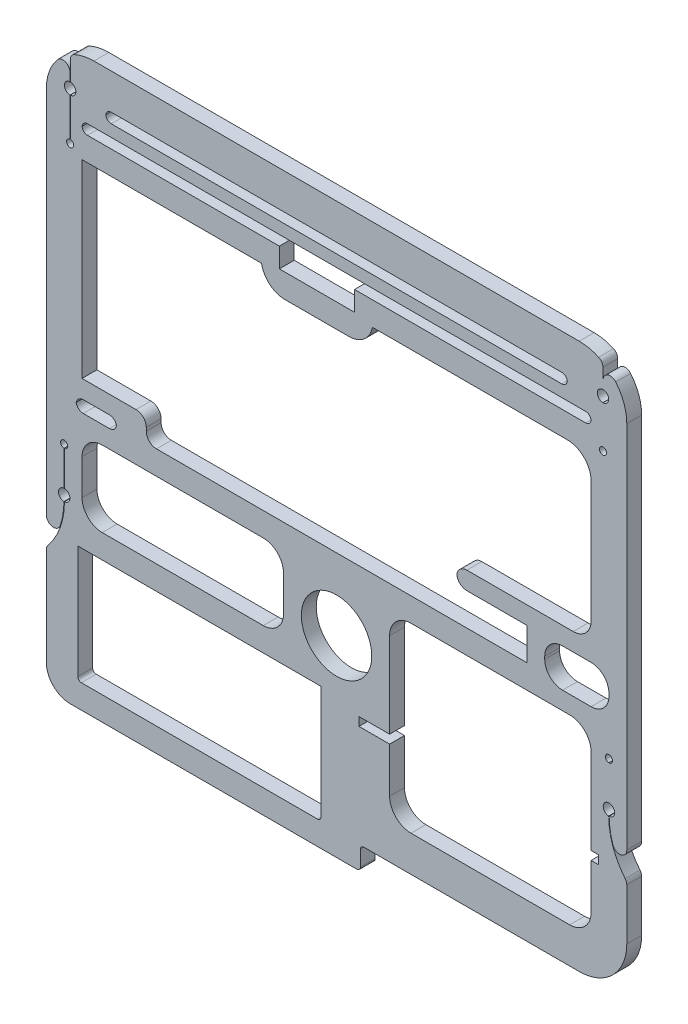
SolidWorks part; units mm, degrees
ref_plane "Front Plane" through (0, 0, 0) normal (0, 0, 1) x (1, 0, 0)
ref_plane "Top Plane" through (0, 0, 0) normal (0, 1, 0) x (1, 0, 0)
ref_plane "Right Plane" through (0, 0, 0) normal (1, 0, 0) x (0, 0, -1)
sketch "Sketch1" plane through (0, 0, 0) normal (0, 0, 1) x (1, 0, 0)
  line L0 (63.9883, 88.3985) -> (63.9883, 84.5885) construction
  line L1 (48.2422, 30.1083) -> (110.2188, 30.1083)
  line L2 (48.2422, 30.1083) -> (48.2422, 88.3985)
  line L3 (48.2422, 88.3985) -> (110.2188, 88.3985)
  line L4 (110.2188, 30.1083) -> (110.2188, 88.3985)
  line L5 (106.4088, 84.5885) -> (52.0522, 84.5885)
  line L6 (106.4088, 84.5885) -> (106.4088, 33.9183)
  line L7 (106.4088, 33.9183) -> (52.0522, 33.9183)
  line L8 (52.0522, 84.5885) -> (52.0522, 33.9183)
  line L9 (63.9883, 86.4935) -> (18.0707, 86.4935) construction
  line L10 (52.0522, 41.2855) -> (48.2422, 41.2855) construction
  line L11 (50.1472, 41.2855) -> (50.1472, 25.8577) construction
  line L12 (13.5248, 33.9183) -> (13.5248, 30.1083) construction
  line L13 (13.5248, 32.0133) -> (21.1598, 32.0133) construction
  line L14 (110.2188, 38.1916) -> (106.4088, 38.1916) construction
  line L15 (108.3138, 38.1916) -> (108.3138, 22.3321) construction
  line L16 (106.4088, 54.6152) -> (106.4088, 79.5085) construction
  line L17 (52.0522, 74.5555) -> (52.0522, 54.6152) construction
  line L22 (79.0876, 86.4935) -> (79.6338, 86.4935) construction
  line L23 (96.5564, 32.0133) -> (96.0102, 32.0133) construction
  dimension "D1" = 3.81
  dimension "D2" = 3.81
extrude "Boss-Extrude1" add sketch "Sketch1" along normal blind 1.5875
sketch "Sketch2" plane through (0, 0, 0) normal (0, 0, -1) x (-1, 0, 0)
  line L0 (-106.4088, 33.9183) -> (-106.4088, 84.5885) construction
  line L1 (-106.4088, 55.8724) -> (-52.0522, 55.8724)
  line L2 (-106.4088, 55.8724) -> (-106.4088, 53.3324)
  line L3 (-106.4088, 53.3324) -> (-52.0522, 53.3324)
  line L4 (-52.0522, 55.8724) -> (-52.0522, 53.3324)
  line L5 (-52.0522, 84.5885) -> (-52.0522, 33.9183) construction
  line L7 (-99.5505, 55.8724) -> (-58.9105, 55.8724) construction
  line L8 (-99.4108, 81.1849) -> (-61.0568, 81.1849) construction
  line L9 (-80.5132, 79.0767) -> (-73.7568, 79.0767) construction
  line L10 (-80.5132, 81.1849) -> (-80.5132, 79.0767) construction
  line L11 (-106.4088, 81.1849) -> (-81.1482, 81.1849)
  line L12 (-106.4088, 81.1849) -> (-106.4088, 78.6449)
  line L13 (-106.4088, 78.6449) -> (-83.0532, 78.6449)
  line L14 (-52.0522, 81.1849) -> (-52.0522, 78.6449)
  line L15 (-106.4088, 83.5217) -> (-52.0522, 83.5217)
  line L16 (-106.4088, 83.5217) -> (-106.4088, 82.2517)
  line L17 (-106.4088, 82.2517) -> (-52.0522, 82.2517)
  line L18 (-52.0522, 83.5217) -> (-52.0522, 82.2517)
  line L19 (-73.7568, 79.0767) -> (-73.7568, 81.1849) construction
  line L20 (-80.5132, 81.1849) -> (-80.5132, 79.0767) construction
  line L21 (-73.7568, 79.0767) -> (-73.7568, 81.1849) construction
  line L22 (-81.1482, 79.0767) -> (-81.1482, 81.1849)
  line L23 (-73.1218, 79.0767) -> (-81.1482, 79.0767)
  line L24 (-73.1218, 79.0767) -> (-73.1218, 81.1849)
  line L25 (-83.0532, 78.6449) -> (-83.0532, 76.5367)
  line L26 (-83.0532, 76.5367) -> (-71.2168, 76.5367)
  line L27 (-71.2168, 76.5367) -> (-71.2168, 78.6449)
  line L28 (-71.2168, 78.6449) -> (-52.0522, 78.6449)
  line L29 (-73.1218, 81.1849) -> (-52.0522, 81.1849)
  line L30 (-81.1482, 71.7401) -> (-80.5132, 71.7401) construction
  line L31 (-57.9086, 84.5885) -> (-57.9086, 83.5217) construction
  line L32 (-73.7568, 71.6584) -> (-73.1218, 71.6584) construction
  line L33 (-106.4088, 84.5885) -> (-52.0522, 84.5885) construction
  line L35 (-57.9086, 82.2517) -> (-57.9086, 81.1849) construction
  dimension "D1" = 2.54
  dimension "D2" = 1.905
  dimension "D3" = 2.54
  dimension "D4" = 1.905
  dimension "D5" = 1.27
  dimension "D6" = 0.635
extrude "Boss-Extrude2" add sketch "Sketch2" against normal up to surface (1.5875 mm away) up to face at (79.2305, 59.2534, 1.5875)
sketch "Sketch14" plane through (0, 0, 1.5875) normal (0, 0, 1) x (1, 0, 0)
  line L0 (77.0492, 42.694) -> (51.5984, 42.694) construction
  line L1 (84.8947, 41.932) -> (84.8947, 50.7924) construction
  line L2 (84.8947, 33.9183) -> (84.8947, 53.3324)
  line L4 (77.0492, 42.694) -> (52.0522, 42.694)
  line L5 (52.0522, 53.3324) -> (52.0522, 33.9183) construction
  line L6 (52.0522, 53.3324) -> (106.4088, 53.3324) construction
  line L7 (52.0522, 33.9183) -> (106.4088, 33.9183) construction
  line L9 (77.0492, 42.694) -> (77.0492, 33.9183)
  line L10 (77.0492, 33.9183) -> (84.8947, 33.9183)
  line L11 (52.0522, 53.3324) -> (84.8947, 53.3324)
  line L12 (52.0522, 53.3324) -> (52.0522, 42.694)
extrude "Boss-Extrude9" add sketch "Sketch14" against normal up to surface (1.5875 mm away) up to face at (78.1827, 80.9246, 0)
sketch "Sketch5" plane through (0, 0, 0) normal (0, 0, -1) x (-1, 0, 0)
  line L1 (-51.5984, 30.2353) -> (-77.5572, 30.2353) construction
  line L2 (-51.5984, 30.2353) -> (-51.5984, 42.694) construction
  line L6 (-51.5984, 42.694) -> (-77.5572, 42.694) construction
  line L7 (-77.5572, 30.2353) -> (-77.5572, 42.694) construction
  line L8 (-51.5984, 30.2353) -> (-77.5572, 30.2353)
  line L9 (-51.5984, 30.2353) -> (-51.5984, 42.694)
  line L10 (-51.5984, 42.694) -> (-77.5572, 42.694)
  line L11 (-77.5572, 30.2353) -> (-77.5572, 42.694)
  circle A1 centre (-79.2305, 48.2171) radius 3.7592 construction
  circle A2 centre (-79.2305, 48.2171) radius 3.7592
extrude "Cut-Extrude1" cut sketch "Sketch5" against normal up to surface (1.5875 mm away) up to face at (64.5507, 38.3062, 1.5875)
fillet "Fillet1" radius 5.08 3 edges at (110.2188, 30.1083, 0.7937) (48.2422, 88.3985, 0.7937) (110.2188, 88.3985, 0.7937)
fillet "Fillet2" radius 2.54 3 edges at (71.2168, 76.5367, 0.7937) (106.4088, 78.6449, 0.7937) (83.0532, 76.5367, 0.7937)
fillet "Fillet4" radius 0.5842 4 edges at (52.0522, 81.1849, 0.7937) (52.0522, 82.2517, 0.7938) (106.4088, 82.2517, 0.7937) (106.4088, 81.1849, 0.7937)
sketch "Sketch6" plane through (0, 0, 0) normal (0, 0, -1) x (-1, 0, 0)
  circle A0 centre (-107.6788, 84.5885) radius 0.6096 construction
  circle A1 centre (-50.7822, 84.5885) radius 0.6096 construction
  circle A2 centre (-108.3138, 46.6777) radius 0.6096 construction
  circle A3 centre (-50.1472, 46.6777) radius 0.6096 construction
  circle A4 centre (-107.6788, 84.5885) radius 0.6096
  circle A5 centre (-50.7822, 84.5885) radius 0.6096
  circle A6 centre (-108.3138, 46.6777) radius 0.6096
  circle A7 centre (-50.1472, 46.6777) radius 0.6096
extrude "Cut-Extrude2" cut sketch "Sketch6" against normal up to surface (1.5875 mm away) up to face at (75.4713, 48.2171, 1.5875)
sketch "Sketch9" plane through (0, 0, 1.5875) normal (0, 0, 1) x (1, 0, 0)
  line L4 (107.199, 41.932) -> (81.6212, 41.932)
  line L5 (81.6212, 41.932) -> (81.6212, 41.0176)
  line L6 (81.6212, 41.0176) -> (107.199, 41.0176)
  line L7 (107.199, 41.0176) -> (107.199, 41.932)
  line L8 (107.199, 41.932) -> (81.6212, 41.932)
  line L9 (81.6212, 41.932) -> (81.6212, 41.0176)
  line L10 (81.6212, 41.0176) -> (107.199, 41.0176)
  line L11 (107.199, 41.0176) -> (107.199, 41.932)
  dimension "D1" = 0
extrude "Cut-Extrude3" cut sketch "Sketch9" against normal up to surface (1.5875 mm away) up to face at (49.5376, 46.6777, 0)
sketch "Sketch11" plane through (0, 0, 1.5875) normal (0, 0, 1) x (1, 0, 0)
  line L0 (51.5984, 30.2353) -> (77.5572, 30.2353) construction
  line L1 (48.2422, 30.1083) -> (81.7705, 30.1083)
  line L2 (48.2422, 30.1083) -> (48.2422, 27.6953)
  line L3 (48.2422, 27.6953) -> (81.7705, 27.6953)
  line L4 (81.7705, 30.1083) -> (81.7705, 27.6953)
  line L5 (79.2305, 51.9763) -> (79.2305, -22.2214) construction
  circle A0 centre (79.2305, 48.2171) radius 3.7592 construction
  dimension "D1" = 2.54
  dimension "D2" = 2.54
extrude "Boss-Extrude6" add sketch "Sketch11" against normal up to surface (1.5875 mm away) up to face at (95.2379, 42.1917, 0)
fillet "Fillet7" radius 2.54 1 edges at (48.2422, 27.6953, 0.7937)
fillet "Fillet8" radius 0.381 2 edges at (81.7705, 27.6953, 0.7937) (81.7705, 30.1083, 0.7937)
sketch "Sketch12" plane through (0, 0, 1.5875) normal (0, 0, 1) x (1, 0, 0)
  line L0 (52.0522, 84.5885) -> (52.0522, 83.5217) construction
  line L1 (52.0522, 84.5885) -> (54.5922, 84.5885)
  line L2 (52.0522, 84.5885) -> (52.0522, 83.5217)
  line L3 (52.0522, 83.5217) -> (54.5922, 83.5217)
  line L4 (54.5922, 84.5885) -> (54.5922, 83.5217)
  line L5 (106.4088, 84.5885) -> (52.0522, 84.5885) construction
  line L6 (106.4088, 83.5217) -> (52.0522, 83.5217) construction
  line L8 (106.4088, 84.5885) -> (103.8688, 84.5885)
  line L9 (106.4088, 84.5885) -> (106.4088, 83.5217)
  line L10 (106.4088, 83.5217) -> (103.8688, 83.5217)
  line L11 (103.8688, 84.5885) -> (103.8688, 83.5217)
  dimension "D1" = 2.54
extrude "Boss-Extrude7" add sketch "Sketch12" against normal up to surface (1.5875 mm away) up to face at (95.2379, 42.1917, 0)
fillet "Fillet11" radius 0.5842 4 edges at (103.8688, 83.5217, 0.7937) (103.8688, 84.5885, 0.7937) (54.5922, 83.5217, 0.7937) (54.5922, 84.5885, 0.7937)
sketch "Sketch13" plane through (0, 0, 1.5875) normal (0, 0, 1) x (1, 0, 0)
  line L0 (50.7695, 86.0858) -> (50.7695, 85.198) construction
  line L1 (50.7949, 85.198) -> (50.7949, 87.2592) construction
  line L2 (50.7695, 83.9791) -> (50.7695, 79.8893) construction
  line L3 (50.7949, 79.8893) -> (50.7949, 83.9791) construction
  line L4 (107.6661, 85.198) -> (107.6661, 87.2592) construction
  line L5 (107.6915, 83.9791) -> (107.6915, 79.8893) construction
  line L6 (107.6661, 79.8893) -> (107.6661, 83.9791) construction
  line L7 (108.3265, 50.9963) -> (108.3265, 47.2872) construction
  line L8 (108.3011, 50.9963) -> (108.3011, 47.2872) construction
  line L9 (50.1345, 50.9963) -> (50.1345, 47.2872) construction
  line L10 (50.1599, 50.9963) -> (50.1599, 47.2872) construction
  line L11 (50.7695, 86.0858) -> (50.7695, 85.198)
  line L12 (50.7949, 85.198) -> (50.7949, 87.2592)
  line L13 (50.7695, 83.9791) -> (50.7695, 79.8893)
  line L14 (50.7949, 79.8893) -> (50.7949, 83.9791)
  line L15 (107.6661, 85.198) -> (107.6661, 87.2592)
  line L16 (107.6915, 83.9791) -> (107.6915, 79.8893)
  line L17 (107.6661, 79.8893) -> (107.6661, 83.9791)
  line L18 (108.3265, 50.9963) -> (108.3265, 47.2872)
  line L19 (108.3011, 50.9963) -> (108.3011, 47.2872)
  line L20 (50.1345, 50.9963) -> (50.1345, 47.2872)
  line L21 (50.1599, 50.9963) -> (50.1599, 47.2872)
  line L22 (48.2422, 83.3185) -> (48.2422, 30.2353) construction
  line L23 (110.2188, 35.1883) -> (110.2188, 83.3185) construction
  line L24 (48.2422, 43.8754) -> (48.2422, 40.6699)
  line L25 (110.2188, 40.6699) -> (110.2188, 43.8754)
  line L26 (107.6915, 83.9791) -> (107.6915, 79.8893)
  line L27 (107.6915, 86.0858) -> (107.6915, 85.198) construction
  line L28 (107.6915, 86.0858) -> (107.6915, 85.198)
  arc A0 (107.6661, 83.9791) -> (107.6915, 83.9791) centre (107.6788, 84.5885) ccw
  arc A1 (50.7695, 86.0858) -> (49.4225, 86.5742) centre (50.0075, 86.0858) ccw construction
  arc A2 (51.2454, 87.9546) -> (50.7949, 87.2592) centre (51.5569, 87.2592) ccw construction
  arc A3 (50.7695, 79.8893) -> (50.7949, 79.8893) centre (50.7822, 79.5085) ccw construction
  arc A4 (107.6661, 87.2592) -> (107.2156, 87.9546) centre (106.9041, 87.2592) ccw construction
  arc A5 (109.0384, 86.5742) -> (107.6915, 86.0858) centre (108.4535, 86.0858) ccw construction
  arc A6 (107.6661, 79.8893) -> (107.6915, 79.8893) centre (107.6788, 79.5085) ccw construction
  arc A7 (108.3265, 50.9963) -> (108.3011, 50.9963) centre (108.3138, 51.3771) ccw construction
  arc A8 (108.3392, 46.0687) -> (108.7338, 43.6346) centre (116.0396, 46.0681) ccw construction
  arc A9 (108.7338, 43.6346) -> (110.2188, 43.8754) centre (109.4568, 43.8754) ccw construction
  arc A10 (108.2884, 46.0687) -> (110.046, 41.153) centre (116.0396, 46.0681) ccw construction
  arc A11 (110.2188, 40.6699) -> (110.046, 41.153) centre (109.4568, 40.6699) ccw construction
  arc A12 (48.2422, 43.8754) -> (49.7271, 43.6346) centre (49.0042, 43.8754) ccw construction
  arc A13 (50.1599, 50.9963) -> (50.1345, 50.9963) centre (50.1472, 51.3771) ccw construction
  arc A14 (48.415, 41.153) -> (50.1726, 46.0687) centre (42.4214, 46.0681) ccw construction
  arc A15 (49.7271, 43.6346) -> (50.1218, 46.0687) centre (42.4214, 46.0681) ccw construction
  arc A16 (48.415, 41.153) -> (48.2422, 40.6699) centre (49.0042, 40.6699) ccw construction
  arc A17 (50.7695, 83.9791) -> (50.7949, 83.9791) centre (50.7822, 84.5885) ccw
  arc A18 (50.7695, 86.0858) -> (49.4225, 86.5742) centre (50.0075, 86.0858) ccw
  arc A19 (51.2454, 87.9546) -> (50.7949, 87.2592) centre (51.5569, 87.2592) ccw
  arc A20 (50.7695, 79.8893) -> (50.7949, 79.8893) centre (50.7822, 79.5085) ccw
  arc A21 (107.6661, 87.2592) -> (107.2156, 87.9546) centre (106.9041, 87.2592) ccw
  arc A22 (109.0384, 86.5742) -> (107.6915, 86.0858) centre (108.4535, 86.0858) ccw
  arc A23 (107.6661, 79.8893) -> (107.6915, 79.8893) centre (107.6788, 79.5085) ccw
  arc A24 (108.3265, 50.9963) -> (108.3011, 50.9963) centre (108.3138, 51.3771) ccw
  arc A25 (108.3392, 46.0687) -> (108.7338, 43.6346) centre (116.0396, 46.0681) ccw
  arc A26 (108.7338, 43.6346) -> (110.2188, 43.8754) centre (109.4568, 43.8754) ccw
  arc A27 (108.2884, 46.0687) -> (110.046, 41.153) centre (116.0396, 46.0681) ccw
  arc A28 (110.2188, 40.6699) -> (110.046, 41.153) centre (109.4568, 40.6699) ccw
  arc A29 (48.2422, 43.8754) -> (49.7271, 43.6346) centre (49.0042, 43.8754) ccw
  arc A30 (50.1599, 50.9963) -> (50.1345, 50.9963) centre (50.1472, 51.3771) ccw
  arc A31 (48.415, 41.153) -> (50.1726, 46.0687) centre (42.4214, 46.0681) ccw
  arc A32 (49.7271, 43.6346) -> (50.1218, 46.0687) centre (42.4214, 46.0681) ccw
  arc A33 (48.415, 41.153) -> (48.2422, 40.6699) centre (49.0042, 40.6699) ccw
  circle A34 centre (50.7822, 84.5885) radius 0.6096 construction
  circle A35 centre (107.6788, 84.5885) radius 0.6096 construction
  circle A36 centre (108.3138, 46.6777) radius 0.6096 construction
  circle A37 centre (50.1472, 46.6777) radius 0.6096 construction
  arc A38 (53.3222, 88.3985) -> (48.2422, 83.3185) centre (53.3222, 83.3185) ccw construction
  arc A39 (110.2188, 83.3185) -> (105.1388, 88.3985) centre (105.1388, 83.3185) ccw construction
  arc A40 (50.7949, 85.198) -> (50.7695, 85.198) centre (50.7822, 84.5885) ccw
  arc A41 (107.6661, 83.9791) -> (107.6915, 83.9791) centre (107.6788, 84.5885) ccw
  arc A42 (108.3265, 47.2872) -> (108.3011, 47.2872) centre (108.3138, 46.6777) ccw
  arc A43 (50.1218, 46.0687) -> (50.1726, 46.0687) centre (50.1472, 46.6777) ccw
  arc A44 (51.2454, 87.9546) -> (49.4225, 86.5742) centre (53.3222, 83.3185) ccw
  arc A45 (109.0384, 86.5742) -> (107.2156, 87.9546) centre (105.1388, 83.3185) ccw
  arc A46 (50.1599, 47.2872) -> (50.1345, 47.2872) centre (50.1472, 46.6777) ccw
  arc A47 (108.2884, 46.0687) -> (108.3392, 46.0687) centre (108.3138, 46.6777) ccw
  arc A48 (107.6915, 85.198) -> (107.6661, 85.198) centre (107.6788, 84.5885) ccw
extrude "Cut-Extrude4" cut sketch "Sketch13" against normal through all contours A48 L28 A22 A45 A21 L15 | L17 A23 L16 A0 | A47 A27 A28 L25 A26 A25 | A42 L18 A24 L19 | A43 A32 A29 L24 A33 A31 | A46 L21 A30 L20 | A19 A44 A18 L11 A40 L12 | L13 A20 L14 A17 region at (50.4642, 87.0334, 1.5875) region at (50.7822, 79.9586, 1.5875) region at (107.9968, 87.0334, 1.5875) region at (107.6788, 79.9586, 1.5875) region at (108.3138, 50.9944, 1.5875) region at (50.1472, 50.9944, 1.5875) region at (48.8136, 42.5993, 1.5875) region at (109.6474, 42.5993, 1.5875)
fillet "Fillet12" radius 2.286 4 edges at (106.4088, 33.9183, 0.7937) (106.4088, 53.3324, 0.7937) (84.8947, 33.9183, 0.7937) (84.8947, 53.3324, 0.7937)
fillet "Fillet13" radius 0.381 2 edges at (51.5984, 30.2353, 0.7937) (77.5572, 30.2353, 0.7937)
sketch "Sketch15" plane through (0, 0, 1.5875) normal (0, 0, 1) x (1, 0, 0)
  line L0 (73.5663, 51.1734) -> (73.5663, 47.393) construction
  line L1 (71.4073, 45.234) -> (54.2112, 45.234) construction
  line L2 (52.0522, 51.1734) -> (52.0522, 47.393) construction
  line L3 (54.2112, 53.3324) -> (71.4073, 53.3324) construction
  line L4 (73.5663, 51.1734) -> (73.5663, 47.393)
  line L5 (71.4073, 45.234) -> (54.2112, 45.234)
  line L6 (52.0522, 51.1734) -> (52.0522, 47.393)
  line L7 (54.2112, 53.3324) -> (71.4073, 53.3324)
  arc A0 (73.5663, 51.1734) -> (71.4073, 53.3324) centre (71.4073, 51.1734) ccw construction
  arc A1 (71.4073, 45.234) -> (73.5663, 47.393) centre (71.4073, 47.393) ccw construction
  arc A2 (52.0522, 47.393) -> (54.2112, 45.234) centre (54.2112, 47.393) ccw construction
  arc A3 (54.2112, 53.3324) -> (52.0522, 51.1734) centre (54.2112, 51.1734) ccw construction
  arc A4 (73.5663, 51.1734) -> (71.4073, 53.3324) centre (71.4073, 51.1734) ccw
  arc A5 (71.4073, 45.234) -> (73.5663, 47.393) centre (71.4073, 47.393) ccw
  arc A6 (52.0522, 47.393) -> (54.2112, 45.234) centre (54.2112, 47.393) ccw
  arc A7 (54.2112, 53.3324) -> (52.0522, 51.1734) centre (54.2112, 51.1734) ccw
extrude "Cut-Extrude5" cut sketch "Sketch15" against normal through all
sketch "Sketch18" plane through (0, 0, 0) normal (0, 0, -1) x (-1, 0, 0)
  line L0 (-99.5505, 55.8724) -> (-99.5505, 59.3268)
  line L1 (-99.5505, 59.3268) -> (-106.4088, 59.3268)
  line L2 (-106.4088, 55.8724) -> (-106.4088, 76.1049) construction
  line L6 (-106.4088, 55.8724) -> (-106.4088, 59.3268)
  line L7 (-99.5505, 56.7868) -> (-58.9105, 56.7868) construction
  line L8 (-99.5505, 56.7868) -> (-99.5505, 55.8724) construction
  line L9 (-106.4088, 55.8724) -> (-99.5505, 55.8724)
  line L20 (-52.0522, 55.8724) -> (-52.0522, 78.6449)
  line L21 (-106.4088, 55.8724) -> (-52.0522, 55.8724)
  line L25 (-73.7198, 76.5367) -> (-80.5502, 76.5367)
  line L26 (-106.4088, 76.1049) -> (-106.4088, 55.8724)
  line L27 (-83.0532, 78.6449) -> (-103.8688, 78.6449)
  line L28 (-73.7198, 76.5367) -> (-80.5502, 76.5367)
  line L29 (-52.0522, 78.6449) -> (-71.2168, 78.6449)
  line L30 (-52.0522, 78.6449) -> (-71.2168, 78.6449)
  arc A9 (-83.0532, 78.6449) -> (-80.5502, 76.5367) centre (-80.5502, 79.0767) ccw
  arc A10 (-83.0532, 78.6449) -> (-80.5502, 76.5367) centre (-80.5502, 79.0767) ccw
  arc A11 (-73.7198, 76.5367) -> (-71.2168, 78.6449) centre (-73.7198, 79.0767) ccw
  arc A12 (-103.8688, 78.6449) -> (-106.4088, 76.1049) centre (-103.8688, 76.1049) ccw
  arc A13 (-73.7198, 76.5367) -> (-71.2168, 78.6449) centre (-73.7198, 79.0767) ccw
  dimension "D3" = 2.54
  dimension "D4" = 0
extrude "Boss-Extrude11" add sketch "Sketch18" against normal up to surface (1.5875 mm away) contours L0 L1 L6 region at (102.9796, 57.5996, 0) up to face at (62.8092, 49.2832, 1.5875)
sketch "Sketch19" plane through (0, 0, 0) normal (0, 0, -1) x (-1, 0, 0)
  line L1 (-58.9102, 58.4124) -> (-58.9102, 55.8724)
  line L2 (-52.0522, 55.8724) -> (-99.5505, 55.8724) construction
  line L4 (-52.0522, 58.4124) -> (-52.0522, 55.8724)
  line L5 (-52.0522, 55.8724) -> (-58.9102, 55.8724)
  line L7 (-58.9102, 58.4124) -> (-52.0522, 58.4124)
  dimension "D1" = 2.54
  dimension "D2" = 6.858
extrude "Boss-Extrude12" add sketch "Sketch19" against normal up to surface (1.5875 mm away) contours L7 L1 L5 region at (55.4812, 57.1424, 0) up to face at (84.4507, 70.3426, 1.5875)
sketch "Sketch20" plane through (0, 0, 0) normal (0, 0, -1) x (-1, 0, 0)
  line L0 (-58.9102, 56.3296) -> (-55.7352, 56.3296) construction
  line L1 (-55.7352, 56.5074) -> (-51.4172, 56.5074)
  line L2 (-55.7352, 56.5074) -> (-55.7352, 55.2374)
  line L3 (-55.7352, 55.2374) -> (-51.4172, 55.2374)
  line L4 (-51.4172, 56.5074) -> (-51.4172, 55.2374)
  line L6 (-48.2422, 83.3185) -> (-48.2422, 43.8754) construction
  line L7 (-51.4172, 56.3296) -> (-48.2422, 56.3296) construction
  line L8 (-54.9256, 56.5074) -> (-54.9256, 58.4124) construction
  line L9 (-58.9102, 58.4124) -> (-58.9102, 55.8724) construction
  line L11 (-54.6333, 55.2374) -> (-54.6333, 53.3324) construction
  line L12 (-71.4073, 53.3324) -> (-54.2112, 53.3324) construction
  line L13 (-58.9102, 58.4124) -> (-52.0522, 58.4124) construction
  point P8 (-55.7352, 55.8724)
  dimension "D1" = 3.175
  dimension "D2" = 1.905
extrude "Cut-Extrude7" cut sketch "Sketch20" against normal through all
fillet "Fillet16" radius 0.762 4 edges at (55.7352, 55.2374, 0.7938) (51.4172, 56.5074, 0.7938) (51.4172, 55.2374, 0.7937) (55.7352, 56.5074, 0.7938)
sketch "Sketch21" plane through (0, 0, 0) normal (0, 0, -1) x (-1, 0, 0)
  line L0 (-99.5505, 59.3268) -> (-92.0575, 59.3268)
  line L1 (-92.0575, 59.3268) -> (-92.0575, 61.2318)
  line L2 (-92.0575, 61.2318) -> (-106.4088, 61.2318)
  line L3 (-106.4088, 59.3268) -> (-106.4088, 76.1049) construction
  line L4 (-99.5505, 59.3268) -> (-106.4088, 59.3268) construction
  line L5 (-99.5505, 59.3268) -> (-106.4088, 59.3268)
  line L6 (-92.0575, 59.3268) -> (-92.0575, 56.7868) construction
  line L9 (-106.4088, 59.3268) -> (-106.4088, 76.1049) construction
  line L10 (-106.4088, 59.3268) -> (-106.4088, 61.2318)
  dimension "D1" = 1.905
extrude "Boss-Extrude13" add sketch "Sketch21" against normal up to surface (1.5875 mm away) up to face at (53.5762, 55.8724, 1.5875)
sketch "Sketch22" plane through (0, 0, 0) normal (0, 0, -1) x (-1, 0, 0)
  line L0 (-102.1969, 61.2318) -> (-102.1969, 59.3268) construction
  line L1 (-108.3138, 59.3268) -> (-101.4555, 59.3268)
  line L2 (-108.3138, 59.3268) -> (-108.3138, 55.2374)
  line L3 (-101.4555, 55.2374) -> (-108.3138, 55.2374)
  line L4 (-101.4555, 59.3268) -> (-101.4555, 55.2374)
  line L5 (-92.0575, 61.2318) -> (-106.4088, 61.2318) construction
  line L6 (-99.5505, 58.1323) -> (-101.4555, 58.1323) construction
  line L7 (-102.1969, 55.2374) -> (-102.1969, 53.3324) construction
  line L9 (-104.1228, 53.3324) -> (-87.1807, 53.3324) construction
  line L10 (-99.5505, 55.8724) -> (-99.5505, 59.3268) construction
  line L12 (-108.3138, 58.1323) -> (-110.2188, 58.1323) construction
  line L13 (-110.2188, 43.8754) -> (-110.2188, 83.3185) construction
  dimension "D1" = 1.905
  dimension "D2" = 1.905
extrude "Cut-Extrude8" cut sketch "Sketch22" against normal through all
fillet "Fillet19" radius 1.905 5 edges at (108.3138, 59.3268, 0.7938) (108.3138, 55.2374, 0.7938) (101.4555, 55.2374, 0.7937) (101.4555, 59.3268, 0.7938) (106.4088, 61.2318, 0.7938)
fillet "Fillet20" radius 1.0922 4 edges at (58.9102, 58.4124, 0.7938) (92.0575, 59.3268, 0.7938) (92.0575, 61.2318, 0.7938) (58.9102, 55.8724, 0.7938)
